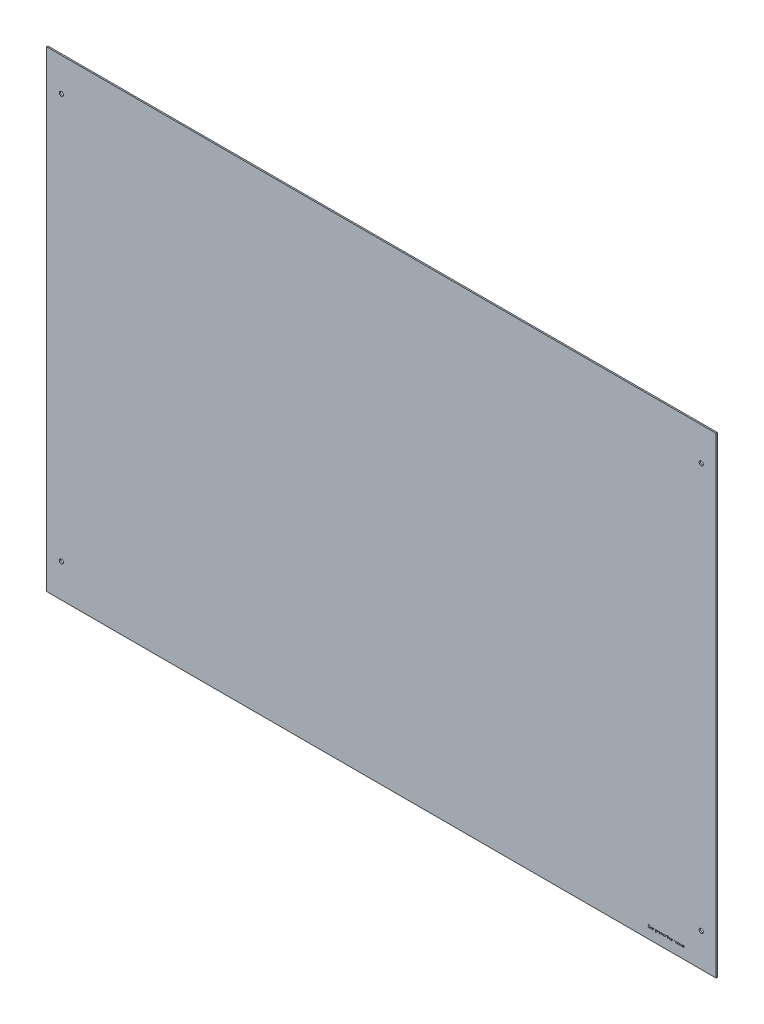
SolidWorks part; units mm, degrees
ref_plane "Front Plane" through (0, 0, 0) normal (0, 0, 1) x (1, 0, 0)
ref_plane "Top Plane" through (0, 0, 0) normal (0, 1, 0) x (1, 0, 0)
ref_plane "Right Plane" through (0, 0, 0) normal (1, 0, 0) x (0, 0, -1)
sketch "Sketch1" plane through (0, 0, 0) normal (0, 0, 1) x (1, 0, 0)
  line L0 (22, 655) -> (926.344, 655) construction
  line L1 (0, 0) -> (1000, 0)
  line L2 (0, 0) -> (0, 705)
  line L3 (0, 705) -> (1000, 705)
  line L4 (1000, 0) -> (1000, 705)
  line L5 (22, 655) -> (22, -22.1798) construction
  line L6 (22, 50) -> (969.7641, 50) construction
  line L7 (978, 655) -> (978, 40.8746) construction
  circle A0 centre (22, 655) radius 3.1
  circle A1 centre (22, 50) radius 3.1
  circle A2 centre (978, 50) radius 3.1
  circle A3 centre (978, 655) radius 3.1
  dimension "D7" = 6.2
  dimension "D1" = 1000
  dimension "D2" = 705
  dimension "D3" = 22
  dimension "D4" = 22
  dimension "D5" = 50
  dimension "D6" = 50
extrude "Boss-Extrude1" add sketch "Sketch1" along normal blind 2
sketch "Sketch2" plane through (0, 0, 2) normal (0, 0, 1) x (1, 0, 0)
  line L0 (897.8686, 15.1529) -> (992.3579, 15.1529) construction
  line L1 (901.5481, 18.0106) -> (901.2733, 17.8003)
  line L2 (901.2733, 16.0054) -> (901.5481, 15.7972)
  line L3 (905.3622, 17.7106) -> (905.6763, 17.7106)
  line L4 (905.6763, 17.7106) -> (905.6763, 17.266)
  line L5 (909.1763, 16.5383) -> (909.1763, 15.1529)
  line L6 (909.1763, 15.1529) -> (908.8622, 15.1529)
  line L7 (908.8622, 15.1529) -> (908.8622, 16.5397)
  line L8 (907.4263, 16.1478) -> (907.4263, 15.1529)
  line L9 (907.4263, 15.1529) -> (907.1122, 15.1529)
  line L10 (907.1122, 15.1529) -> (907.1122, 16.4534)
  line L11 (905.6763, 16.2291) -> (905.6763, 15.1529)
  line L12 (905.6763, 15.1529) -> (905.3622, 15.1529)
  line L13 (905.3622, 15.1529) -> (905.3622, 17.7106)
  line L14 (909.8942, 17.7106) -> (910.2083, 17.7106)
  line L15 (910.2083, 17.7106) -> (910.2083, 17.2373)
  line L16 (910.2083, 15.6163) -> (910.2083, 14.2106)
  line L17 (910.2083, 14.2106) -> (909.8942, 14.2106)
  line L18 (909.8942, 14.2106) -> (909.8942, 17.7106)
  line L19 (913.125, 17.7106) -> (913.4391, 17.7106)
  line L20 (913.4391, 17.7106) -> (913.4391, 17.3341)
  line L21 (914.3366, 17.6678) -> (914.1641, 17.3958)
  line L22 (913.4391, 16.0124) -> (913.4391, 15.1529)
  line L23 (913.4391, 15.1529) -> (913.125, 15.1529)
  line L24 (913.125, 15.1529) -> (913.125, 17.7106)
  line L25 (916.7498, 15.9606) -> (917.0289, 15.814)
  line L26 (917.1635, 16.3644) -> (914.875, 16.3644)
  line L27 (914.908, 16.6785) -> (916.8494, 16.6785)
  line L28 (919.0032, 17.3915) -> (918.7901, 17.1721)
  line L29 (917.5673, 15.4543) -> (917.7756, 15.6913)
  line L30 (920.8878, 17.3915) -> (920.6747, 17.1721)
  line L31 (919.4519, 15.4543) -> (919.6602, 15.6913)
  line L32 (924.6571, 17.7106) -> (924.9712, 17.7106)
  line L33 (924.9712, 17.7106) -> (924.9712, 17.3341)
  line L34 (925.8686, 17.6678) -> (925.6961, 17.3958)
  line L35 (924.9712, 16.0124) -> (924.9712, 15.1529)
  line L36 (924.9712, 15.1529) -> (924.6571, 15.1529)
  line L37 (924.6571, 15.1529) -> (924.6571, 17.7106)
  line L38 (928.6058, 18.7216) -> (928.6058, 18.3949)
  line L39 (928.0246, 18.0653) -> (928.0246, 17.7106)
  line L40 (928.0246, 17.7106) -> (928.5609, 17.7106)
  line L41 (928.5609, 17.7106) -> (928.5609, 17.3965)
  line L42 (928.5609, 17.3965) -> (928.0239, 17.3965)
  line L43 (928.0239, 17.3965) -> (928.0224, 15.1529)
  line L44 (928.0224, 15.1529) -> (927.7083, 15.1529)
  line L45 (927.7083, 15.1529) -> (927.7083, 17.3965)
  line L46 (927.7083, 17.3965) -> (927.3494, 17.3965)
  line L47 (927.3494, 17.3965) -> (927.3494, 17.7106)
  line L48 (927.3494, 17.7106) -> (927.7083, 17.7106)
  line L49 (927.7083, 17.7106) -> (927.7083, 18.1193)
  line L50 (928.9648, 17.7106) -> (929.2789, 17.7106)
  line L51 (929.2789, 17.7106) -> (929.2789, 17.3341)
  line L52 (930.1763, 17.6678) -> (930.0038, 17.3958)
  line L53 (929.2789, 16.0124) -> (929.2789, 15.1529)
  line L54 (929.2789, 15.1529) -> (928.9648, 15.1529)
  line L55 (928.9648, 15.1529) -> (928.9648, 17.7106)
  line L56 (933.6763, 17.7106) -> (933.9904, 17.7106)
  line L57 (933.9904, 17.7106) -> (933.9904, 17.2492)
  line L58 (935.9199, 16.4591) -> (935.9199, 15.1529)
  line L59 (935.9199, 15.1529) -> (935.6058, 15.1529)
  line L60 (935.6058, 15.1529) -> (935.6058, 16.356)
  line L61 (933.9904, 16.0776) -> (933.9904, 15.1529)
  line L62 (933.9904, 15.1529) -> (933.6763, 15.1529)
  line L63 (933.6763, 15.1529) -> (933.6763, 17.7106)
  line L64 (936.9519, 18.7426) -> (937.266, 18.7426)
  line L65 (937.266, 18.7426) -> (937.266, 17.7106)
  line L66 (937.266, 17.7106) -> (937.7148, 17.7106)
  line L67 (937.7148, 17.7106) -> (937.7148, 17.3965)
  line L68 (937.7148, 17.3965) -> (937.266, 17.3965)
  line L69 (937.266, 17.3965) -> (937.266, 15.1529)
  line L70 (937.266, 15.1529) -> (936.9519, 15.1529)
  line L71 (936.9519, 15.1529) -> (936.9519, 17.3965)
  line L72 (936.9519, 17.3965) -> (936.5032, 17.3965)
  line L73 (936.5032, 17.3965) -> (936.5032, 17.7106)
  line L74 (936.5032, 17.7106) -> (936.9519, 17.7106)
  line L75 (936.9519, 17.7106) -> (936.9519, 18.7426)
  line L76 (942.1122, 17.156) -> (941.8493, 16.9926)
  line L77 (941.8493, 15.8708) -> (942.1122, 15.6983)
  line L78 (945.6571, 17.7106) -> (945.9971, 17.7106)
  line L79 (945.9971, 17.7106) -> (946.8462, 15.8484)
  line L80 (946.8462, 15.8484) -> (947.6952, 17.7106)
  line L81 (947.6952, 17.7106) -> (948.0353, 17.7106)
  line L82 (948.0353, 17.7106) -> (946.8686, 15.1529)
  line L83 (946.8686, 15.1529) -> (946.8237, 15.1529)
  line L84 (946.8237, 15.1529) -> (945.6571, 17.7106)
  line L85 (950.6729, 15.9606) -> (950.9519, 15.814)
  line L86 (951.0866, 16.3644) -> (948.7981, 16.3644)
  line L87 (948.831, 16.6785) -> (950.7724, 16.6785)
  line L88 (951.625, 17.7106) -> (951.9391, 17.7106)
  line L89 (951.9391, 17.7106) -> (951.9391, 17.3341)
  line L90 (952.8366, 17.6678) -> (952.6641, 17.3958)
  line L91 (951.9391, 16.0124) -> (951.9391, 15.1529)
  line L92 (951.9391, 15.1529) -> (951.625, 15.1529)
  line L93 (951.625, 15.1529) -> (951.625, 17.7106)
  spline S0 degree 3 poles (901.2733, 17.8003) (901.235, 17.8473) (901.1744, 17.9145) (901.0867, 17.9963) (901.0188, 18.0536) (900.9471, 18.105) (900.8732, 18.1533) (900.796, 18.1965) (900.6892, 18.249) (900.5496, 18.3037) (900.3121, 18.3661) (900.1266, 18.3842) (900.0014, 18.3836) knots 0 0 0 0 0.125475 0.187121 0.248294 0.309295 0.36985 0.430973 0.492456 0.616148 0.740844 1 1 1 1
  spline S1 degree 3 poles (900.0014, 18.3836) (899.9315, 18.3846) (899.8276, 18.3771) (899.6911, 18.3569) (899.5914, 18.3348) (899.4938, 18.3068) (899.3977, 18.2734) (899.3045, 18.232) (899.2129, 18.1863) (899.1251, 18.1347) (899.0421, 18.0784) (898.9641, 18.018) (898.891, 17.9534) (898.8228, 17.8847) (898.76, 17.8114) (898.7028, 17.7335) (898.6501, 17.6522) (898.6029, 17.5677) (898.5634, 17.4796) (898.5284, 17.3895) (898.5007, 17.2963) (898.4788, 17.2008) (898.4583, 17.0686) (898.4511, 16.9676) (898.4519, 16.8994) knots 0 0 0 0 0.087502 0.130463 0.172752 0.215403 0.25765 0.300153 0.343121 0.385925 0.427686 0.468818 0.509492 0.549883 0.58998 0.630405 0.670869 0.711384 0.751627 0.791776 0.832459 0.873319 0.914543 1 1 1 1
  spline S2 degree 3 poles (898.4519, 16.8994) (898.4515, 16.7978) (898.4656, 16.6477) (898.5113, 16.4548) (898.5614, 16.3194) (898.6234, 16.1895) (898.7016, 16.0672) (898.7922, 15.9508) (898.8965, 15.843) (899.0109, 15.7445) (899.1336, 15.6577) (899.2644, 15.5854) (899.4018, 15.5252) (899.5468, 15.479) (899.7535, 15.4346) (899.9142, 15.4212) (900.0232, 15.4221) knots 0 0 0 0 0.12629 0.186726 0.246146 0.305576 0.365429 0.426326 0.48884 0.551725 0.613919 0.675484 0.737334 0.800229 0.864502 1 1 1 1
  spline S3 degree 3 poles (900.0232, 15.4221) (900.1433, 15.4221) (900.3218, 15.439) (900.5497, 15.501) (900.711, 15.5648) (900.8643, 15.6479) (901.0619, 15.7842) (901.1925, 15.9126) (901.2733, 16.0054) knots 0 0 0 0 0.252949 0.374755 0.49594 0.617181 0.740909 1 1 1 1
  spline S4 degree 3 poles (901.5481, 15.7972) (901.5048, 15.7397) (901.436, 15.657) (901.3351, 15.556) (901.2555, 15.4858) (901.1723, 15.4197) (901.0843, 15.3594) (900.9924, 15.3041) (900.897, 15.2534) (900.7983, 15.2085) (900.6963, 15.1701) (900.5915, 15.1369) (900.4838, 15.1097) (900.3731, 15.0884) (900.2203, 15.0691) (900.1037, 15.0626) (900.0253, 15.0631) knots 0 0 0 0 0.123053 0.183475 0.243727 0.304279 0.364863 0.425946 0.487391 0.54922 0.611144 0.673529 0.736961 0.800785 0.866013 1 1 1 1
  spline S5 degree 3 poles (900.0253, 15.0631) (899.9508, 15.0622) (899.8407, 15.0682) (899.6963, 15.0838) (899.5925, 15.101) (899.4914, 15.1213) (899.3938, 15.1486) (899.2989, 15.1792) (899.2069, 15.2151) (899.1178, 15.2556) (899.032, 15.3014) (898.9494, 15.352) (898.8691, 15.4065) (898.7926, 15.4665) (898.6937, 15.5531) (898.6247, 15.6246) (898.5816, 15.6752) knots 0 0 0 0 0.13775 0.203917 0.26878 0.332414 0.394754 0.45618 0.516996 0.577396 0.637198 0.696999 0.756756 0.816554 0.876948 1 1 1 1
  spline S6 degree 3 poles (898.5816, 15.6752) (898.5091, 15.7599) (898.4116, 15.8957) (898.3085, 16.0921) (898.2461, 16.2455) (898.1974, 16.4055) (898.1514, 16.631) (898.1375, 16.8054) (898.1378, 16.9232) knots 0 0 0 0 0.247156 0.36878 0.490734 0.613614 0.738958 1 1 1 1
  spline S7 degree 3 poles (898.1378, 16.9232) (898.1378, 17.047) (898.1535, 17.2305) (898.2103, 17.4659) (898.2696, 17.6321) (898.345, 17.7913) (898.438, 17.9421) (898.5477, 18.0856) (898.6731, 18.2196) (898.8107, 18.3422) (898.958, 18.45) (899.1148, 18.5397) (899.2793, 18.6147) (899.4528, 18.6723) (899.6994, 18.7272) (899.8912, 18.7424) (900.021, 18.7426) knots 0 0 0 0 0.127014 0.187955 0.248014 0.307748 0.368235 0.42947 0.492743 0.556258 0.618217 0.679655 0.741246 0.803415 0.866815 1 1 1 1
  spline S8 degree 3 poles (900.021, 18.7426) (900.1006, 18.7428) (900.2187, 18.7374) (900.3733, 18.7163) (900.4849, 18.6952) (900.594, 18.669) (900.6998, 18.6349) (900.8029, 18.5959) (900.9026, 18.5509) (900.9986, 18.5004) (901.0906, 18.445) (901.1781, 18.3847) (901.2616, 18.3201) (901.3397, 18.2497) (901.4399, 18.1505) (901.5059, 18.0674) (901.5481, 18.0106) knots 0 0 0 0 0.135683 0.201215 0.265682 0.329267 0.392395 0.45507 0.517127 0.57879 0.63974 0.700192 0.759806 0.819628 0.879355 1 1 1 1
  spline S9 degree 3 poles (903.4117, 17.7554) (903.5058, 17.7564) (903.645, 17.7428) (903.8231, 17.6982) (903.9489, 17.653) (904.0673, 17.5923) (904.2197, 17.4947) (904.3213, 17.402) (904.3834, 17.3341) knots 0 0 0 0 0.258332 0.382134 0.503804 0.624693 0.746871 1 1 1 1
  spline S10 degree 3 poles (904.3834, 17.3341) (904.4405, 17.2717) (904.5169, 17.1718) (904.5991, 17.0274) (904.6482, 16.9152) (904.6868, 16.7988) (904.724, 16.6359) (904.7335, 16.5096) (904.734, 16.4247) knots 0 0 0 0 0.253834 0.376506 0.498534 0.621368 0.744565 1 1 1 1
  spline S11 degree 3 poles (904.734, 16.4247) (904.7345, 16.3391) (904.7228, 16.212) (904.6842, 16.0476) (904.6434, 15.9298) (904.591, 15.8159) (904.5271, 15.7065) (904.4512, 15.6013) (904.3652, 15.5013) (904.2702, 15.4092) (904.1671, 15.3288) (904.0579, 15.26) (903.9413, 15.2046) (903.8182, 15.1609) (903.6421, 15.119) (903.5046, 15.1084) (903.4117, 15.108) knots 0 0 0 0 0.123337 0.183265 0.243172 0.302898 0.363774 0.425605 0.489659 0.553785 0.616222 0.677854 0.739517 0.802097 0.865866 1 1 1 1
  spline S12 degree 3 poles (903.4117, 15.108) (903.3183, 15.1084) (903.1802, 15.1189) (903.0037, 15.1609) (902.8805, 15.2047) (902.7634, 15.26) (902.6536, 15.3286) (902.5504, 15.4092) (902.4553, 15.5013) (902.3693, 15.6013) (902.2934, 15.7065) (902.2295, 15.8159) (902.1772, 15.9298) (902.1364, 16.0476) (902.0978, 16.212) (902.086, 16.3391) (902.0866, 16.4247) knots 0 0 0 0 0.134635 0.198324 0.260825 0.322714 0.384555 0.446913 0.510958 0.574931 0.636685 0.697483 0.757134 0.816966 0.876818 1 1 1 1
  spline S13 degree 3 poles (902.0866, 16.4247) (902.087, 16.5094) (902.0966, 16.6354) (902.1336, 16.7979) (902.1723, 16.9138) (902.2218, 17.0256) (902.303, 17.1703) (902.3807, 17.2694) (902.4371, 17.332) knots 0 0 0 0 0.255238 0.378679 0.501088 0.622714 0.746241 1 1 1 1
  spline S14 degree 3 poles (902.4371, 17.332) (902.4987, 17.4008) (902.6013, 17.4926) (902.7533, 17.5922) (902.8729, 17.6517) (902.9986, 17.6985) (903.1775, 17.7428) (903.3171, 17.7563) (903.4117, 17.7554) knots 0 0 0 0 0.252713 0.374819 0.496436 0.617911 0.741288 1 1 1 1
  spline S15 degree 3 poles (903.4103, 17.4413) (903.3433, 17.4412) (903.2437, 17.4321) (903.1158, 17.401) (903.0243, 17.3684) (902.9367, 17.3263) (902.8528, 17.2746) (902.7724, 17.214) (902.697, 17.1445) (902.6278, 17.0686) (902.5673, 16.9878) (902.5159, 16.9033) (902.473, 16.815) (902.4412, 16.7221) (902.4097, 16.592) (902.4008, 16.4907) (902.4007, 16.4226) knots 0 0 0 0 0.126044 0.187165 0.247399 0.30838 0.36978 0.432584 0.497641 0.562401 0.625557 0.687332 0.748313 0.809791 0.871768 1 1 1 1
  spline S16 degree 3 poles (902.4007, 16.4226) (902.4009, 16.3339) (902.4165, 16.2006) (902.4748, 16.0326) (902.5333, 15.913) (902.6068, 15.8023) (902.6933, 15.7037) (902.7919, 15.6185) (902.9015, 15.5478) (903.0199, 15.4917) (903.1883, 15.4378) (903.321, 15.4211) (903.4103, 15.4221) knots 0 0 0 0 0.168179 0.251488 0.335841 0.419834 0.502345 0.583649 0.665931 0.748717 0.831047 1 1 1 1
  spline S17 degree 3 poles (903.4103, 15.4221) (903.4995, 15.4212) (903.6321, 15.4376) (903.8001, 15.4919) (903.9184, 15.5477) (904.0279, 15.6188) (904.1273, 15.7032) (904.213, 15.8026) (904.2864, 15.9132) (904.3459, 16.0324) (904.4039, 16.2007) (904.4197, 16.3339) (904.4199, 16.4226) knots 0 0 0 0 0.168983 0.250908 0.333708 0.416005 0.49766 0.579893 0.663902 0.748466 0.831791 1 1 1 1
  spline S18 degree 3 poles (904.4199, 16.4226) (904.4197, 16.4907) (904.4108, 16.5919) (904.3794, 16.7222) (904.3474, 16.815) (904.3048, 16.9035) (904.2524, 16.9875) (904.1921, 17.0689) (904.1221, 17.1443) (904.0468, 17.214) (903.9664, 17.2746) (903.8826, 17.3261) (903.7952, 17.3688) (903.7037, 17.4007) (903.5762, 17.4323) (903.477, 17.441) (903.4103, 17.4413) knots 0 0 0 0 0.128274 0.19027 0.251768 0.312769 0.374793 0.43797 0.503047 0.568125 0.63095 0.692369 0.752973 0.813641 0.874355 1 1 1 1
  spline S19 degree 3 poles (905.6763, 17.266) (905.729, 17.3415) (905.8354, 17.4744) (905.9654, 17.5845) (906.0311, 17.6257) knots 0 0 0 0 0.543395 1 1 1 1
  spline S20 degree 3 poles (906.0311, 17.6257) (906.1127, 17.6679) (906.2845, 17.7345) (906.4676, 17.7547) (906.5583, 17.7554) knots 0 0 0 0 0.503035 1 1 1 1
  spline S21 degree 3 poles (906.5583, 17.7554) (906.6194, 17.7546) (906.711, 17.7469) (906.8288, 17.7156) (906.9134, 17.6832) (906.9931, 17.6439) (907.0662, 17.5979) (907.1318, 17.5462) (907.19, 17.4865) (907.2422, 17.4172) (907.31, 17.3034) (907.3488, 17.2064) (907.3723, 17.1377) knots 0 0 0 0 0.166532 0.248836 0.331246 0.412957 0.490494 0.566156 0.639987 0.716765 0.802144 1 1 1 1
  spline S22 degree 3 poles (907.3723, 17.1377) (907.3984, 17.1869) (907.4415, 17.2573) (907.5058, 17.3444) (907.5558, 17.4044) (907.6082, 17.4597) (907.6633, 17.5105) (907.7207, 17.557) (907.8005, 17.6113) (907.9043, 17.669) (908.0789, 17.7361) (908.218, 17.7557) (908.3104, 17.7554) knots 0 0 0 0 0.141226 0.209116 0.27484 0.339483 0.402476 0.464942 0.526833 0.647415 0.765562 1 1 1 1
  spline S23 degree 3 poles (908.3104, 17.7554) (908.3941, 17.7548) (908.5191, 17.7411) (908.6733, 17.6831) (908.7788, 17.6249) (908.874, 17.5517) (908.9567, 17.4646) (909.0265, 17.3643) (909.072, 17.2699) (909.103, 17.1866) (909.122, 17.1156) (909.1389, 17.0374) (909.1528, 16.952) (909.163, 16.8591) (909.1736, 16.7205) (909.1767, 16.6126) (909.1763, 16.5383) knots 0 0 0 0 0.147965 0.218797 0.28947 0.359724 0.429708 0.500497 0.574429 0.613947 0.657155 0.703973 0.754939 0.809707 0.868833 1 1 1 1
  spline S24 degree 3 poles (908.8622, 16.5397) (908.8623, 16.6026) (908.8613, 16.6929) (908.8542, 16.8078) (908.8483, 16.882) (908.84, 16.9482) (908.8294, 17.0064) (908.8181, 17.057) (908.7994, 17.1131) (908.7694, 17.175) (908.7238, 17.2417) (908.6663, 17.2998) (908.6, 17.3502) (908.5244, 17.3912) (908.4106, 17.4314) (908.3182, 17.4417) (908.2557, 17.4413) knots 0 0 0 0 0.150563 0.216151 0.27568 0.328707 0.375904 0.417302 0.452693 0.517265 0.581217 0.645322 0.712024 0.78013 0.850218 1 1 1 1
  spline S25 degree 3 poles (908.2557, 17.4413) (908.1772, 17.4427) (908.0602, 17.4234) (907.9132, 17.3654) (907.811, 17.303) (907.717, 17.2282) (907.6361, 17.1393) (907.5693, 17.0386) (907.524, 16.9455) (907.4954, 16.8618) (907.4765, 16.7887) (907.4619, 16.7056) (907.4481, 16.6131) (907.4391, 16.5106) (907.4277, 16.3546) (907.4268, 16.2323) (907.4263, 16.1478) knots 0 0 0 0 0.134707 0.201865 0.270788 0.340024 0.408083 0.476813 0.547346 0.58564 0.628865 0.677153 0.730803 0.789807 0.854325 1 1 1 1
  spline S26 degree 3 poles (907.1122, 16.4534) (907.1122, 16.524) (907.1113, 16.6253) (907.1042, 16.7541) (907.0983, 16.8369) (907.0899, 16.9103) (907.0802, 16.9747) (907.0689, 17.0299) (907.0501, 17.0905) (907.0214, 17.1572) (906.9752, 17.2283) (906.9176, 17.2906) (906.85, 17.3438) (906.774, 17.3877) (906.6596, 17.431) (906.5663, 17.4408) (906.5036, 17.4413) knots 0 0 0 0 0.158779 0.227738 0.289946 0.345499 0.393896 0.436374 0.472122 0.536384 0.599078 0.661948 0.726311 0.791771 0.858647 1 1 1 1
  spline S27 degree 3 poles (906.5036, 17.4413) (906.4278, 17.442) (906.3139, 17.4238) (906.1711, 17.3662) (906.0691, 17.3066) (905.9754, 17.2327) (905.8934, 17.1458) (905.8245, 17.047) (905.7787, 16.9548) (905.7492, 16.8732) (905.7296, 16.8039) (905.7128, 16.7269) (905.7003, 16.642) (905.6882, 16.5498) (905.68, 16.4112) (905.6753, 16.3035) (905.6763, 16.2291) knots 0 0 0 0 0.136871 0.206114 0.277538 0.349772 0.421251 0.492911 0.567027 0.606614 0.649704 0.697303 0.749086 0.804881 0.865485 1 1 1 1
  spline S28 degree 3 poles (910.2083, 17.2373) (910.2705, 17.3226) (910.3749, 17.4385) (910.5362, 17.5627) (910.6633, 17.6341) (910.7978, 17.6879) (910.989, 17.7421) (911.1401, 17.7551) (911.2418, 17.7554) knots 0 0 0 0 0.263045 0.386061 0.505771 0.625178 0.746148 1 1 1 1
  spline S29 degree 3 poles (911.2418, 17.7554) (911.3314, 17.7545) (911.4647, 17.7446) (911.6362, 17.7038) (911.7577, 17.6604) (911.875, 17.6068) (911.9862, 17.5391) (912.0931, 17.4607) (912.193, 17.3704) (912.2854, 17.2728) (912.3652, 17.1678) (912.4341, 17.0588) (912.4897, 16.9442) (912.5333, 16.8249) (912.5753, 16.6572) (912.586, 16.5265) (912.5866, 16.4387) knots 0 0 0 0 0.128636 0.190653 0.252125 0.313446 0.375227 0.438498 0.503285 0.56801 0.630879 0.692154 0.752552 0.813191 0.873985 1 1 1 1
  spline S30 degree 3 poles (912.5866, 16.4387) (912.5863, 16.3492) (912.5748, 16.2165) (912.5342, 16.0458) (912.4912, 15.9245) (912.4355, 15.8085) (912.3678, 15.6979) (912.2879, 15.5927) (912.1966, 15.4944) (912.0976, 15.4038) (911.9917, 15.3246) (911.8806, 15.258) (911.765, 15.2024) (911.6437, 15.1606) (911.4734, 15.1196) (911.3409, 15.1083) (911.2516, 15.108) knots 0 0 0 0 0.128034 0.189574 0.25058 0.311733 0.37325 0.435763 0.500346 0.564949 0.627528 0.689157 0.749865 0.81076 0.8723 1 1 1 1
  spline S31 degree 3 poles (911.2516, 15.108) (911.1511, 15.1068) (911.0026, 15.124) (910.8123, 15.1766) (910.6781, 15.2332) (910.55, 15.3055) (910.3849, 15.425) (910.2759, 15.5362) (910.2083, 15.6163) knots 0 0 0 0 0.250548 0.37123 0.492116 0.613401 0.737997 1 1 1 1
  spline S32 degree 3 poles (911.239, 17.4413) (911.1689, 17.4424) (911.0655, 17.4323) (910.9318, 17.4027) (910.8377, 17.3698) (910.7474, 17.3294) (910.6617, 17.2789) (910.5807, 17.2193) (910.5045, 17.1516) (910.4356, 17.077) (910.3746, 16.9974) (910.3234, 16.9129) (910.2809, 16.8243) (910.2486, 16.7309) (910.2174, 16.5987) (910.2085, 16.4956) (910.2083, 16.4261) knots 0 0 0 0 0.130024 0.192374 0.253884 0.314896 0.375806 0.438242 0.501591 0.564881 0.626533 0.687516 0.748106 0.808796 0.870822 1 1 1 1
  spline S33 degree 3 poles (910.2083, 16.4261) (910.2085, 16.3353) (910.2236, 16.2002) (910.2797, 16.0304) (910.3381, 15.9129) (910.4121, 15.805) (910.5012, 15.7083) (910.6046, 15.6235) (910.7207, 15.552) (910.8451, 15.4941) (911.0183, 15.4384) (911.1538, 15.4223) (911.2439, 15.4221) knots 0 0 0 0 0.169344 0.251061 0.332326 0.413189 0.494299 0.576654 0.661785 0.747765 0.831967 1 1 1 1
  spline S34 degree 3 poles (911.2439, 15.4221) (911.3324, 15.4216) (911.4646, 15.4395) (911.6335, 15.4944) (911.7537, 15.5539) (911.8665, 15.6269) (911.9684, 15.7144) (912.0574, 15.8159) (912.1333, 15.9289) (912.1943, 16.0501) (912.2556, 16.2165) (912.2714, 16.3484) (912.2724, 16.4352) knots 0 0 0 0 0.165574 0.248159 0.332033 0.416257 0.499525 0.583039 0.668596 0.754035 0.83692 1 1 1 1
  spline S35 degree 3 poles (912.2724, 16.4352) (912.2737, 16.5227) (912.2541, 16.6537) (912.1966, 16.8211) (912.1341, 16.9406) (912.0599, 17.0534) (911.9701, 17.1529) (911.8695, 17.2401) (911.7568, 17.3121) (911.6359, 17.3694) (911.4649, 17.4259) (911.3295, 17.4409) (911.239, 17.4413) knots 0 0 0 0 0.163349 0.245826 0.330367 0.415198 0.497941 0.580476 0.66374 0.747513 0.830399 1 1 1 1
  spline S36 degree 3 poles (913.4391, 17.3341) (913.4821, 17.4018) (913.5501, 17.4955) (913.6559, 17.5982) (913.7335, 17.6568) (913.8139, 17.7005) (913.9215, 17.7432) (914.007, 17.755) (914.0631, 17.7554) knots 0 0 0 0 0.306112 0.438367 0.560541 0.675317 0.786114 1 1 1 1
  spline S37 degree 3 poles (914.0631, 17.7554) (914.1081, 17.7551) (914.2046, 17.7382) (914.2922, 17.6947) (914.3366, 17.6678) knots 0 0 0 0 0.463523 1 1 1 1
  spline S38 degree 3 poles (914.1641, 17.3958) (914.1355, 17.4084) (914.084, 17.4317) (914.0282, 17.441) (914.0035, 17.4413) knots 0 0 0 0 0.56023 1 1 1 1
  spline S39 degree 3 poles (914.0035, 17.4413) (913.952, 17.4414) (913.8731, 17.4225) (913.7782, 17.3657) (913.72, 17.3175) (913.675, 17.2709) (913.6428, 17.2303) (913.6133, 17.1847) (913.5852, 17.135) (913.5595, 17.0803) (913.5266, 16.9992) (913.5071, 16.9347) (913.4952, 16.8902) knots 0 0 0 0 0.191338 0.295191 0.410312 0.47193 0.536425 0.603119 0.674118 0.749332 0.828283 1 1 1 1
  spline S40 degree 3 poles (913.4952, 16.8902) (913.4835, 16.8456) (913.472, 16.7704) (913.4598, 16.6607) (913.4526, 16.5577) (913.4461, 16.4411) (913.4408, 16.2579) (913.4386, 16.1134) (913.4391, 16.0124) knots 0 0 0 0 0.156938 0.2586 0.375891 0.508166 0.656238 1 1 1 1
  spline S41 degree 3 poles (917.0289, 15.814) (916.9874, 15.7363) (916.9179, 15.6273) (916.8109, 15.4976) (916.7259, 15.4158) (916.6362, 15.3446) (916.5415, 15.2822) (916.4412, 15.2291) (916.3353, 15.1844) (916.223, 15.15) (916.0606, 15.1167) (915.9338, 15.108) (915.8475, 15.108) knots 0 0 0 0 0.181661 0.265874 0.346355 0.4246 0.501903 0.579992 0.658443 0.738672 0.821894 1 1 1 1
  spline S42 degree 3 poles (915.8475, 15.108) (915.7517, 15.108) (915.6108, 15.119) (915.4315, 15.1622) (915.3083, 15.2061) (915.1936, 15.2635) (915.0871, 15.3335) (914.9883, 15.4156) (914.9002, 15.5106) (914.821, 15.6123) (914.7511, 15.7183) (914.6926, 15.8282) (914.6451, 15.9415) (914.6067, 16.0574) (914.5706, 16.2178) (914.5618, 16.3417) (914.5609, 16.4247) knots 0 0 0 0 0.139629 0.204797 0.268135 0.329814 0.391301 0.453434 0.516552 0.579631 0.641119 0.701294 0.76081 0.819932 0.87892 1 1 1 1
  spline S43 degree 3 poles (914.5609, 16.4247) (914.5619, 16.5025) (914.5691, 16.6186) (914.6008, 16.7692) (914.6329, 16.8781) (914.6745, 16.9836) (914.7427, 17.1211) (914.8078, 17.2172) (914.8554, 17.2787) knots 0 0 0 0 0.253768 0.377428 0.500551 0.623296 0.746578 1 1 1 1
  spline S44 degree 3 poles (914.8554, 17.2787) (914.916, 17.3544) (915.0147, 17.4603) (915.1694, 17.571) (915.291, 17.6391) (915.4213, 17.6907) (915.6078, 17.7432) (915.7557, 17.7542) (915.8552, 17.7554) knots 0 0 0 0 0.253589 0.374643 0.49534 0.616325 0.739759 1 1 1 1
  spline S45 degree 3 poles (915.8552, 17.7554) (915.958, 17.7559) (916.1099, 17.741) (916.3025, 17.6877) (916.4364, 17.6326) (916.562, 17.5614) (916.7203, 17.4423) (916.8237, 17.3327) (916.8851, 17.252) knots 0 0 0 0 0.259033 0.38188 0.502258 0.622752 0.744743 1 1 1 1
  spline S46 degree 3 poles (916.8851, 17.252) (916.931, 17.1931) (916.9909, 17.0975) (917.0545, 16.9607) (917.0929, 16.8518) (917.1239, 16.738) (917.1545, 16.5756) (917.1619, 16.4497) (917.1635, 16.3644) knots 0 0 0 0 0.236255 0.356174 0.47725 0.60154 0.729618 1 1 1 1
  spline S47 degree 3 poles (914.875, 16.3644) (914.8768, 16.2982) (914.8857, 16.2003) (914.916, 16.0751) (914.9472, 15.988) (914.9851, 15.9051) (915.0315, 15.8269) (915.0868, 15.7539) (915.1485, 15.6853) (915.2172, 15.6242) (915.2895, 15.5696) (915.3664, 15.5238) (915.4473, 15.4866) (915.5321, 15.4575) (915.6521, 15.4305) (915.7452, 15.4217) (915.8082, 15.4221) knots 0 0 0 0 0.134476 0.198391 0.260753 0.321829 0.383037 0.444653 0.507398 0.569825 0.630778 0.690929 0.750945 0.811049 0.872331 1 1 1 1
  spline S48 degree 3 poles (915.8082, 15.4221) (915.8704, 15.4218) (915.9637, 15.4291) (916.0855, 15.4546) (916.1748, 15.4805) (916.2604, 15.5121) (916.3396, 15.5502) (916.4125, 15.5923) (916.4806, 15.6405) (916.5467, 15.6996) (916.6402, 15.8044) (916.7073, 15.894) (916.7498, 15.9606) knots 0 0 0 0 0.163879 0.245659 0.327726 0.40861 0.485749 0.559169 0.630268 0.705306 0.792065 1 1 1 1
  spline S49 degree 3 poles (916.8494, 16.6785) (916.8295, 16.7592) (916.7899, 16.8732) (916.7174, 17.0101) (916.6558, 17.0957) (916.586, 17.1717) (916.5054, 17.2381) (916.4149, 17.2975) (916.3152, 17.3477) (916.2095, 17.3903) (916.0617, 17.4289) (915.9477, 17.4425) (915.8713, 17.4413) knots 0 0 0 0 0.185231 0.267501 0.3444 0.419595 0.496891 0.576638 0.660268 0.745387 0.83004 1 1 1 1
  spline S50 degree 3 poles (915.8713, 17.4413) (915.8094, 17.4415) (915.7173, 17.4348) (915.599, 17.4091) (915.5143, 17.3831) (915.4337, 17.3485) (915.3287, 17.2941) (915.2578, 17.2398) (915.2123, 17.2015) knots 0 0 0 0 0.259141 0.384162 0.505992 0.629098 0.750669 1 1 1 1
  spline S51 degree 3 poles (915.2123, 17.2015) (915.1774, 17.1722) (915.1302, 17.1213) (915.0734, 17.0465) (915.0341, 16.9835) (914.998, 16.9149) (914.9518, 16.8142) (914.9244, 16.7338) (914.908, 16.6785) knots 0 0 0 0 0.22258 0.3385 0.458709 0.585535 0.717518 1 1 1 1
  spline S52 degree 3 poles (918.7901, 17.1721) (918.7553, 17.2136) (918.7018, 17.2716) (918.624, 17.3356) (918.5689, 17.3745) (918.5135, 17.4039) (918.4414, 17.4322) (918.3852, 17.4413) (918.3484, 17.4413) knots 0 0 0 0 0.305036 0.441309 0.565963 0.683525 0.793334 1 1 1 1
  spline S53 degree 3 poles (918.3484, 17.4413) (918.3047, 17.4422) (918.2396, 17.4281) (918.1623, 17.3846) (918.1121, 17.3387) (918.0697, 17.2859) (918.028, 17.207) (918.0162, 17.141) (918.016, 17.0971) knots 0 0 0 0 0.245901 0.369166 0.498511 0.628504 0.751028 1 1 1 1
  spline S54 degree 3 poles (918.016, 17.0971) (918.0161, 17.0567) (918.0318, 16.9726) (918.0763, 16.8995) (918.103, 16.865) knots 0 0 0 0 0.479403 1 1 1 1
  spline S55 degree 3 poles (918.103, 16.865) (918.119, 16.8433) (918.1502, 16.8138) (918.1957, 16.7736) (918.239, 16.7416) (918.2878, 16.708) (918.3646, 16.6606) (918.4248, 16.624) (918.4683, 16.6014) knots 0 0 0 0 0.17756 0.283982 0.402217 0.533568 0.676121 1 1 1 1
  spline S56 degree 3 poles (918.4683, 16.6014) (918.521, 16.5723) (918.5968, 16.5284) (918.6905, 16.4655) (918.752, 16.4209) (918.8059, 16.3757) (918.8676, 16.3195) (918.9067, 16.2737) (918.9289, 16.2424) knots 0 0 0 0 0.307115 0.446213 0.574876 0.694152 0.804581 1 1 1 1
  spline S57 degree 3 poles (918.9289, 16.2424) (918.967, 16.1849) (919.031, 16.0582) (919.0471, 15.9172) (919.0481, 15.847) knots 0 0 0 0 0.495235 1 1 1 1
  spline S58 degree 3 poles (919.0481, 15.847) (919.0476, 15.7973) (919.0421, 15.7232) (919.0191, 15.6284) (918.996, 15.5607) (918.9649, 15.4968) (918.9283, 15.435) (918.8844, 15.3766) (918.8343, 15.3217) (918.7795, 15.2717) (918.721, 15.2276) (918.6588, 15.1911) (918.5932, 15.1608) (918.5243, 15.1367) (918.4263, 15.1141) (918.35, 15.1083) (918.2986, 15.108) knots 0 0 0 0 0.127199 0.188597 0.24864 0.309525 0.370037 0.431889 0.495704 0.559519 0.621372 0.682397 0.743568 0.805498 0.86864 1 1 1 1
  spline S59 degree 3 poles (918.2986, 15.108) (918.2283, 15.1075) (918.1231, 15.1196) (917.9876, 15.1583) (917.8892, 15.198) (917.7962, 15.2482) (917.6829, 15.3277) (917.6096, 15.4008) (917.5673, 15.4543) knots 0 0 0 0 0.251724 0.377219 0.504694 0.631458 0.755401 1 1 1 1
  spline S60 degree 3 poles (917.7756, 15.6913) (917.8132, 15.6494) (917.8715, 15.5907) (917.9573, 15.5273) (918.0202, 15.4886) (918.0844, 15.4589) (918.1709, 15.4309) (918.238, 15.4219) (918.2825, 15.4221) knots 0 0 0 0 0.285904 0.417172 0.540501 0.659238 0.775006 1 1 1 1
  spline S61 degree 3 poles (918.2825, 15.4221) (918.3417, 15.4216) (918.4295, 15.4369) (918.5352, 15.4886) (918.6032, 15.5427) (918.6611, 15.6056) (918.7172, 15.7) (918.7343, 15.7804) (918.734, 15.8337) knots 0 0 0 0 0.261896 0.387836 0.517686 0.644509 0.764718 1 1 1 1
  spline S62 degree 3 poles (918.734, 15.8337) (918.7338, 15.8776) (918.7198, 15.9659) (918.6756, 16.0437) (918.6477, 16.0776) knots 0 0 0 0 0.500453 1 1 1 1
  spline S63 degree 3 poles (918.6477, 16.0776) (918.6309, 16.0979) (918.5997, 16.1273) (918.5518, 16.1654) (918.5067, 16.1978) (918.4547, 16.2314) (918.372, 16.28) (918.3064, 16.3168) (918.26, 16.3413) knots 0 0 0 0 0.167462 0.27227 0.389551 0.520801 0.666263 1 1 1 1
  spline S64 degree 3 poles (918.26, 16.3413) (918.2094, 16.3692) (918.1364, 16.4109) (918.0474, 16.4726) (917.9883, 16.5155) (917.9361, 16.5589) (917.8782, 16.6153) (917.84, 16.6594) (917.819, 16.6904) knots 0 0 0 0 0.30595 0.443775 0.572824 0.692154 0.802296 1 1 1 1
  spline S65 degree 3 poles (917.819, 16.6904) (917.7798, 16.7468) (917.7214, 16.8747) (917.7007, 17.0137) (917.7019, 17.0845) knots 0 0 0 0 0.492591 1 1 1 1
  spline S66 degree 3 poles (917.7019, 17.0845) (917.7023, 17.1306) (917.7064, 17.1992) (917.7271, 17.2868) (917.7461, 17.3489) (917.7726, 17.4074) (917.8042, 17.4631) (917.8414, 17.5158) (917.8843, 17.5648) (917.9314, 17.6093) (917.9823, 17.6481) (918.0358, 17.6812) (918.0922, 17.709) (918.152, 17.73) (918.2372, 17.7497) (918.3035, 17.756) (918.3484, 17.7554) knots 0 0 0 0 0.133044 0.196507 0.258613 0.319728 0.380873 0.442636 0.505079 0.567881 0.628814 0.68891 0.748765 0.809386 0.870884 1 1 1 1
  spline S67 degree 3 poles (918.3484, 17.7554) (918.4033, 17.7554) (918.4871, 17.7437) (918.595, 17.7052) (918.6774, 17.665) (918.7592, 17.6129) (918.8727, 17.5261) (918.9526, 17.4488) (919.0032, 17.3915) knots 0 0 0 0 0.213412 0.326127 0.444452 0.569061 0.702712 1 1 1 1
  spline S68 degree 3 poles (920.6747, 17.1721) (920.6399, 17.2136) (920.5864, 17.2716) (920.5086, 17.3356) (920.4535, 17.3745) (920.3981, 17.4039) (920.326, 17.4322) (920.2698, 17.4413) (920.233, 17.4413) knots 0 0 0 0 0.305036 0.441309 0.565963 0.683525 0.793334 1 1 1 1
  spline S69 degree 3 poles (920.233, 17.4413) (920.1893, 17.4422) (920.1242, 17.4281) (920.0469, 17.3846) (919.9967, 17.3387) (919.9543, 17.2859) (919.9126, 17.207) (919.9008, 17.141) (919.9007, 17.0971) knots 0 0 0 0 0.245901 0.369166 0.498511 0.628504 0.751028 1 1 1 1
  spline S70 degree 3 poles (919.9007, 17.0971) (919.9007, 17.0567) (919.9164, 16.9726) (919.9609, 16.8995) (919.9876, 16.865) knots 0 0 0 0 0.479403 1 1 1 1
  spline S71 degree 3 poles (919.9876, 16.865) (920.0036, 16.8433) (920.0348, 16.8138) (920.0804, 16.7736) (920.1236, 16.7416) (920.1724, 16.708) (920.2493, 16.6606) (920.3095, 16.624) (920.3529, 16.6014) knots 0 0 0 0 0.17756 0.283982 0.402217 0.533568 0.676121 1 1 1 1
  spline S72 degree 3 poles (920.3529, 16.6014) (920.4056, 16.5723) (920.4815, 16.5284) (920.5751, 16.4655) (920.6366, 16.4209) (920.6905, 16.3757) (920.7522, 16.3195) (920.7914, 16.2737) (920.8135, 16.2424) knots 0 0 0 0 0.307115 0.446213 0.574876 0.694152 0.804581 1 1 1 1
  spline S73 degree 3 poles (920.8135, 16.2424) (920.8516, 16.1849) (920.9156, 16.0582) (920.9317, 15.9172) (920.9327, 15.847) knots 0 0 0 0 0.495235 1 1 1 1
  spline S74 degree 3 poles (920.9327, 15.847) (920.9322, 15.7973) (920.9267, 15.7232) (920.9037, 15.6284) (920.8807, 15.5607) (920.8495, 15.4968) (920.8129, 15.435) (920.7691, 15.3766) (920.719, 15.3217) (920.6641, 15.2717) (920.6056, 15.2276) (920.5434, 15.1911) (920.4778, 15.1608) (920.4089, 15.1367) (920.3109, 15.1141) (920.2346, 15.1083) (920.1832, 15.108) knots 0 0 0 0 0.127199 0.188597 0.24864 0.309525 0.370037 0.431889 0.495704 0.559519 0.621372 0.682397 0.743568 0.805498 0.86864 1 1 1 1
  spline S75 degree 3 poles (920.1832, 15.108) (920.1129, 15.1075) (920.0077, 15.1196) (919.8722, 15.1583) (919.7738, 15.198) (919.6808, 15.2482) (919.5675, 15.3277) (919.4942, 15.4008) (919.4519, 15.4543) knots 0 0 0 0 0.251724 0.377219 0.504694 0.631458 0.755401 1 1 1 1
  spline S76 degree 3 poles (919.6602, 15.6913) (919.6978, 15.6494) (919.7561, 15.5907) (919.842, 15.5273) (919.9048, 15.4886) (919.969, 15.4589) (920.0555, 15.4309) (920.1226, 15.4219) (920.1671, 15.4221) knots 0 0 0 0 0.285904 0.417172 0.540501 0.659238 0.775006 1 1 1 1
  spline S77 degree 3 poles (920.1671, 15.4221) (920.2263, 15.4216) (920.3141, 15.4369) (920.4198, 15.4886) (920.4879, 15.5427) (920.5457, 15.6056) (920.6018, 15.7) (920.6189, 15.7804) (920.6186, 15.8337) knots 0 0 0 0 0.261896 0.387836 0.517686 0.644509 0.764718 1 1 1 1
  spline S78 degree 3 poles (920.6186, 15.8337) (920.6184, 15.8776) (920.6044, 15.9659) (920.5603, 16.0437) (920.5324, 16.0776) knots 0 0 0 0 0.500453 1 1 1 1
  spline S79 degree 3 poles (920.5324, 16.0776) (920.5155, 16.0979) (920.4843, 16.1273) (920.4364, 16.1654) (920.3913, 16.1978) (920.3393, 16.2314) (920.2566, 16.28) (920.191, 16.3168) (920.1446, 16.3413) knots 0 0 0 0 0.167462 0.27227 0.389551 0.520801 0.666263 1 1 1 1
  spline S80 degree 3 poles (920.1446, 16.3413) (920.0941, 16.3692) (920.0211, 16.4109) (919.932, 16.4726) (919.8729, 16.5155) (919.8208, 16.5589) (919.7628, 16.6153) (919.7246, 16.6594) (919.7036, 16.6904) knots 0 0 0 0 0.30595 0.443775 0.572824 0.692154 0.802296 1 1 1 1
  spline S81 degree 3 poles (919.7036, 16.6904) (919.6644, 16.7468) (919.606, 16.8747) (919.5853, 17.0137) (919.5866, 17.0845) knots 0 0 0 0 0.492591 1 1 1 1
  spline S82 degree 3 poles (919.5866, 17.0845) (919.5869, 17.1306) (919.591, 17.1992) (919.6117, 17.2868) (919.6307, 17.3489) (919.6572, 17.4074) (919.6889, 17.4631) (919.726, 17.5158) (919.7689, 17.5648) (919.816, 17.6093) (919.8669, 17.6481) (919.9204, 17.6812) (919.9768, 17.709) (920.0367, 17.73) (920.1218, 17.7497) (920.1881, 17.756) (920.233, 17.7554) knots 0 0 0 0 0.133044 0.196507 0.258613 0.319728 0.380873 0.442636 0.505079 0.567881 0.628814 0.68891 0.748765 0.809386 0.870884 1 1 1 1
  spline S83 degree 3 poles (920.233, 17.7554) (920.2879, 17.7554) (920.3718, 17.7437) (920.4797, 17.7052) (920.562, 17.665) (920.6438, 17.6129) (920.7573, 17.5261) (920.8372, 17.4488) (920.8878, 17.3915) knots 0 0 0 0 0.213412 0.326127 0.444452 0.569061 0.702712 1 1 1 1
  spline S84 degree 3 poles (922.7963, 17.7554) (922.8904, 17.7564) (923.0296, 17.7428) (923.2077, 17.6982) (923.3335, 17.653) (923.4519, 17.5923) (923.6043, 17.4947) (923.7059, 17.402) (923.768, 17.3341) knots 0 0 0 0 0.258332 0.382134 0.503804 0.624693 0.746871 1 1 1 1
  spline S85 degree 3 poles (923.768, 17.3341) (923.8251, 17.2717) (923.9015, 17.1718) (923.9837, 17.0274) (924.0328, 16.9152) (924.0715, 16.7988) (924.1086, 16.6359) (924.1181, 16.5096) (924.1186, 16.4247) knots 0 0 0 0 0.253834 0.376506 0.498534 0.621368 0.744565 1 1 1 1
  spline S86 degree 3 poles (924.1186, 16.4247) (924.1191, 16.3391) (924.1074, 16.212) (924.0688, 16.0476) (924.028, 15.9298) (923.9756, 15.8159) (923.9117, 15.7065) (923.8359, 15.6013) (923.7499, 15.5013) (923.6548, 15.4092) (923.5517, 15.3288) (923.4425, 15.26) (923.3259, 15.2046) (923.2028, 15.1609) (923.0268, 15.119) (922.8892, 15.1084) (922.7963, 15.108) knots 0 0 0 0 0.123337 0.183265 0.243172 0.302898 0.363774 0.425605 0.489659 0.553785 0.616222 0.677854 0.739517 0.802097 0.865866 1 1 1 1
  spline S87 degree 3 poles (922.7963, 15.108) (922.7029, 15.1084) (922.5649, 15.1189) (922.3883, 15.1609) (922.2651, 15.2047) (922.148, 15.26) (922.0382, 15.3286) (921.935, 15.4092) (921.8399, 15.5013) (921.7539, 15.6013) (921.678, 15.7065) (921.6142, 15.8159) (921.5618, 15.9298) (921.521, 16.0476) (921.4824, 16.212) (921.4707, 16.3391) (921.4712, 16.4247) knots 0 0 0 0 0.134635 0.198324 0.260825 0.322714 0.384555 0.446913 0.510958 0.574931 0.636685 0.697483 0.757134 0.816966 0.876818 1 1 1 1
  spline S88 degree 3 poles (921.4712, 16.4247) (921.4717, 16.5094) (921.4812, 16.6354) (921.5182, 16.7979) (921.5569, 16.9138) (921.6065, 17.0256) (921.6876, 17.1703) (921.7653, 17.2694) (921.8217, 17.332) knots 0 0 0 0 0.255238 0.378679 0.501088 0.622714 0.746241 1 1 1 1
  spline S89 degree 3 poles (921.8217, 17.332) (921.8833, 17.4008) (921.9859, 17.4926) (922.1379, 17.5922) (922.2576, 17.6517) (922.3832, 17.6985) (922.5621, 17.7428) (922.7017, 17.7563) (922.7963, 17.7554) knots 0 0 0 0 0.252713 0.374819 0.496436 0.617911 0.741288 1 1 1 1
  spline S90 degree 3 poles (922.7949, 17.4413) (922.7279, 17.4412) (922.6284, 17.4321) (922.5004, 17.401) (922.4089, 17.3684) (922.3213, 17.3263) (922.2374, 17.2746) (922.157, 17.214) (922.0816, 17.1445) (922.0124, 17.0686) (921.9519, 16.9878) (921.9005, 16.9033) (921.8577, 16.815) (921.8258, 16.7221) (921.7943, 16.592) (921.7855, 16.4907) (921.7853, 16.4226) knots 0 0 0 0 0.126044 0.187165 0.247399 0.30838 0.36978 0.432584 0.497641 0.562401 0.625557 0.687332 0.748313 0.809791 0.871768 1 1 1 1
  spline S91 degree 3 poles (921.7853, 16.4226) (921.7855, 16.3339) (921.8011, 16.2006) (921.8594, 16.0326) (921.918, 15.913) (921.9914, 15.8023) (922.0779, 15.7037) (922.1765, 15.6185) (922.2861, 15.5478) (922.4045, 15.4917) (922.5729, 15.4378) (922.7056, 15.4211) (922.7949, 15.4221) knots 0 0 0 0 0.168179 0.251488 0.335841 0.419834 0.502345 0.583649 0.665931 0.748717 0.831047 1 1 1 1
  spline S92 degree 3 poles (922.7949, 15.4221) (922.8842, 15.4212) (923.0167, 15.4376) (923.1848, 15.4919) (923.303, 15.5477) (923.4126, 15.6188) (923.5119, 15.7032) (923.5977, 15.8026) (923.671, 15.9132) (923.7305, 16.0324) (923.7885, 16.2007) (923.8043, 16.3339) (923.8045, 16.4226) knots 0 0 0 0 0.168983 0.250908 0.333708 0.416005 0.49766 0.579893 0.663902 0.748466 0.831791 1 1 1 1
  spline S93 degree 3 poles (923.8045, 16.4226) (923.8043, 16.4907) (923.7954, 16.5919) (923.764, 16.7222) (923.7321, 16.815) (923.6894, 16.9035) (923.637, 16.9875) (923.5768, 17.0689) (923.5067, 17.1443) (923.4314, 17.214) (923.351, 17.2746) (923.2672, 17.3261) (923.1798, 17.3688) (923.0884, 17.4007) (922.9608, 17.4323) (922.8616, 17.441) (922.7949, 17.4413) knots 0 0 0 0 0.128274 0.19027 0.251768 0.312769 0.374793 0.43797 0.503047 0.568125 0.63095 0.692369 0.752973 0.813641 0.874355 1 1 1 1
  spline S94 degree 3 poles (924.9712, 17.3341) (925.0142, 17.4018) (925.0821, 17.4955) (925.1879, 17.5982) (925.2656, 17.6568) (925.346, 17.7005) (925.4535, 17.7432) (925.5391, 17.755) (925.5952, 17.7554) knots 0 0 0 0 0.306112 0.438367 0.560541 0.675317 0.786114 1 1 1 1
  spline S95 degree 3 poles (925.5952, 17.7554) (925.6401, 17.7551) (925.7366, 17.7382) (925.8243, 17.6947) (925.8686, 17.6678) knots 0 0 0 0 0.463523 1 1 1 1
  spline S96 degree 3 poles (925.6961, 17.3958) (925.6675, 17.4084) (925.616, 17.4317) (925.5603, 17.441) (925.5356, 17.4413) knots 0 0 0 0 0.56023 1 1 1 1
  spline S97 degree 3 poles (925.5356, 17.4413) (925.484, 17.4414) (925.4052, 17.4225) (925.3102, 17.3657) (925.252, 17.3175) (925.207, 17.2709) (925.1749, 17.2303) (925.1454, 17.1847) (925.1172, 17.135) (925.0916, 17.0803) (925.0587, 16.9992) (925.0392, 16.9347) (925.0273, 16.8902) knots 0 0 0 0 0.191338 0.295191 0.410312 0.47193 0.536425 0.603119 0.674118 0.749332 0.828283 1 1 1 1
  spline S98 degree 3 poles (925.0273, 16.8902) (925.0155, 16.8456) (925.004, 16.7704) (924.9918, 16.6607) (924.9847, 16.5577) (924.9781, 16.4411) (924.9728, 16.2579) (924.9706, 16.1134) (924.9712, 16.0124) knots 0 0 0 0 0.156938 0.2586 0.375891 0.508166 0.656238 1 1 1 1
  spline S99 degree 3 poles (928.6058, 18.3949) (928.5497, 18.4183) (928.446, 18.4561) (928.3367, 18.4732) (928.2875, 18.4734) knots 0 0 0 0 0.553028 1 1 1 1
  spline S100 degree 3 poles (928.2875, 18.4734) (928.2573, 18.4722) (928.2128, 18.47) (928.1586, 18.4519) (928.1237, 18.4349) (928.0947, 18.4136) (928.0699, 18.3921) (928.052, 18.3679) (928.0422, 18.3454) (928.0363, 18.3245) (928.0345, 18.3032) (928.0301, 18.277) (928.0289, 18.2448) (928.0261, 18.2077) (928.0263, 18.1471) (928.0231, 18.0993) (928.0246, 18.0653) knots 0 0 0 0 0.158724 0.229424 0.297719 0.360776 0.416988 0.468546 0.516675 0.544534 0.581509 0.628334 0.683433 0.749506 0.822818 1 1 1 1
  spline S101 degree 3 poles (927.7083, 18.1193) (927.7075, 18.1628) (927.7106, 18.2255) (927.7147, 18.3059) (927.7205, 18.3585) (927.7271, 18.4064) (927.7367, 18.4488) (927.7457, 18.4868) (927.762, 18.5299) (927.7865, 18.5788) (927.826, 18.6304) (927.8734, 18.6767) (927.93, 18.7157) (927.9937, 18.7481) (928.0909, 18.7801) (928.1697, 18.7866) (928.223, 18.7875) knots 0 0 0 0 0.133856 0.192948 0.247916 0.296642 0.341504 0.38163 0.416905 0.483173 0.548917 0.616062 0.686302 0.759645 0.83539 1 1 1 1
  spline S102 degree 3 poles (928.223, 18.7875) (928.2819, 18.7868) (928.4117, 18.7747) (928.5376, 18.7409) (928.6058, 18.7216) knots 0 0 0 0 0.453863 1 1 1 1
  spline S103 degree 3 poles (929.2789, 17.3341) (929.3219, 17.4018) (929.3898, 17.4955) (929.4956, 17.5982) (929.5733, 17.6568) (929.6536, 17.7005) (929.7612, 17.7432) (929.8468, 17.755) (929.9029, 17.7554) knots 0 0 0 0 0.306112 0.438367 0.560541 0.675317 0.786114 1 1 1 1
  spline S104 degree 3 poles (929.9029, 17.7554) (929.9478, 17.7551) (930.0443, 17.7382) (930.132, 17.6947) (930.1763, 17.6678) knots 0 0 0 0 0.463523 1 1 1 1
  spline S105 degree 3 poles (930.0038, 17.3958) (929.9752, 17.4084) (929.9237, 17.4317) (929.8679, 17.441) (929.8433, 17.4413) knots 0 0 0 0 0.56023 1 1 1 1
  spline S106 degree 3 poles (929.8433, 17.4413) (929.7917, 17.4414) (929.7129, 17.4225) (929.6179, 17.3657) (929.5597, 17.3175) (929.5147, 17.2709) (929.4826, 17.2303) (929.4531, 17.1847) (929.4249, 17.135) (929.3992, 17.0803) (929.3664, 16.9992) (929.3469, 16.9347) (929.3349, 16.8902) knots 0 0 0 0 0.191338 0.295191 0.410312 0.47193 0.536425 0.603119 0.674118 0.749332 0.828283 1 1 1 1
  spline S107 degree 3 poles (929.3349, 16.8902) (929.3232, 16.8456) (929.3117, 16.7704) (929.2995, 16.6607) (929.2924, 16.5577) (929.2858, 16.4411) (929.2805, 16.2579) (929.2783, 16.1134) (929.2789, 16.0124) knots 0 0 0 0 0.156938 0.2586 0.375891 0.508166 0.656238 1 1 1 1
  spline S108 degree 3 poles (931.7258, 17.7554) (931.8199, 17.7564) (931.9591, 17.7428) (932.1372, 17.6982) (932.263, 17.653) (932.3814, 17.5923) (932.5338, 17.4947) (932.6354, 17.402) (932.6975, 17.3341) knots 0 0 0 0 0.258332 0.382134 0.503804 0.624693 0.746871 1 1 1 1
  spline S109 degree 3 poles (932.6975, 17.3341) (932.7546, 17.2717) (932.831, 17.1718) (932.9132, 17.0274) (932.9623, 16.9152) (933.0009, 16.7988) (933.0381, 16.6359) (933.0476, 16.5096) (933.0481, 16.4247) knots 0 0 0 0 0.253834 0.376506 0.498534 0.621368 0.744565 1 1 1 1
  spline S110 degree 3 poles (933.0481, 16.4247) (933.0486, 16.3391) (933.0369, 16.212) (932.9983, 16.0476) (932.9575, 15.9298) (932.9051, 15.8159) (932.8412, 15.7065) (932.7653, 15.6013) (932.6793, 15.5013) (932.5843, 15.4092) (932.4812, 15.3288) (932.372, 15.26) (932.2554, 15.2046) (932.1323, 15.1609) (931.9563, 15.119) (931.8187, 15.1084) (931.7258, 15.108) knots 0 0 0 0 0.123337 0.183265 0.243172 0.302898 0.363774 0.425605 0.489659 0.553785 0.616222 0.677854 0.739517 0.802097 0.865866 1 1 1 1
  spline S111 degree 3 poles (931.7258, 15.108) (931.6324, 15.1084) (931.4944, 15.1189) (931.3178, 15.1609) (931.1946, 15.2047) (931.0775, 15.26) (930.9677, 15.3286) (930.8645, 15.4092) (930.7694, 15.5013) (930.6834, 15.6013) (930.6075, 15.7065) (930.5436, 15.8159) (930.4913, 15.9298) (930.4505, 16.0476) (930.4119, 16.212) (930.4001, 16.3391) (930.4007, 16.4247) knots 0 0 0 0 0.134635 0.198324 0.260825 0.322714 0.384555 0.446913 0.510958 0.574931 0.636685 0.697483 0.757134 0.816966 0.876818 1 1 1 1
  spline S112 degree 3 poles (930.4007, 16.4247) (930.4011, 16.5094) (930.4107, 16.6354) (930.4477, 16.7979) (930.4864, 16.9138) (930.5359, 17.0256) (930.6171, 17.1703) (930.6948, 17.2694) (930.7512, 17.332) knots 0 0 0 0 0.255238 0.378679 0.501088 0.622714 0.746241 1 1 1 1
  spline S113 degree 3 poles (930.7512, 17.332) (930.8128, 17.4008) (930.9154, 17.4926) (931.0674, 17.5922) (931.187, 17.6517) (931.3127, 17.6985) (931.4916, 17.7428) (931.6312, 17.7563) (931.7258, 17.7554) knots 0 0 0 0 0.252713 0.374819 0.496436 0.617911 0.741288 1 1 1 1
  spline S114 degree 3 poles (931.7244, 17.4413) (931.6574, 17.4412) (931.5578, 17.4321) (931.4299, 17.401) (931.3384, 17.3684) (931.2508, 17.3263) (931.1669, 17.2746) (931.0865, 17.214) (931.0111, 17.1445) (930.9419, 17.0686) (930.8814, 16.9878) (930.83, 16.9033) (930.7871, 16.815) (930.7553, 16.7221) (930.7238, 16.592) (930.7149, 16.4907) (930.7148, 16.4226) knots 0 0 0 0 0.126044 0.187165 0.247399 0.30838 0.36978 0.432584 0.497641 0.562401 0.625557 0.687332 0.748313 0.809791 0.871768 1 1 1 1
  spline S115 degree 3 poles (930.7148, 16.4226) (930.715, 16.3339) (930.7306, 16.2006) (930.7889, 16.0326) (930.8474, 15.913) (930.9209, 15.8023) (931.0074, 15.7037) (931.106, 15.6185) (931.2156, 15.5478) (931.334, 15.4917) (931.5024, 15.4378) (931.6351, 15.4211) (931.7244, 15.4221) knots 0 0 0 0 0.168179 0.251488 0.335841 0.419834 0.502345 0.583649 0.665931 0.748717 0.831047 1 1 1 1
  spline S116 degree 3 poles (931.7244, 15.4221) (931.8136, 15.4212) (931.9462, 15.4376) (932.1142, 15.4919) (932.2325, 15.5477) (932.342, 15.6188) (932.4414, 15.7032) (932.5271, 15.8026) (932.6005, 15.9132) (932.66, 16.0324) (932.718, 16.2007) (932.7338, 16.3339) (932.734, 16.4226) knots 0 0 0 0 0.168983 0.250908 0.333708 0.416005 0.49766 0.579893 0.663902 0.748466 0.831791 1 1 1 1
  spline S117 degree 3 poles (932.734, 16.4226) (932.7338, 16.4907) (932.7249, 16.5919) (932.6935, 16.7222) (932.6615, 16.815) (932.6189, 16.9035) (932.5665, 16.9875) (932.5062, 17.0689) (932.4362, 17.1443) (932.3609, 17.214) (932.2805, 17.2746) (932.1967, 17.3261) (932.1093, 17.3688) (932.0178, 17.4007) (931.8903, 17.4323) (931.7911, 17.441) (931.7244, 17.4413) knots 0 0 0 0 0.128274 0.19027 0.251768 0.312769 0.374793 0.43797 0.503047 0.568125 0.63095 0.692369 0.752973 0.813641 0.874355 1 1 1 1
  spline S118 degree 3 poles (933.9904, 17.2492) (934.0538, 17.3314) (934.1546, 17.4463) (934.312, 17.5669) (934.4319, 17.637) (934.5576, 17.6898) (934.7331, 17.7414) (934.8711, 17.755) (934.9636, 17.7554) knots 0 0 0 0 0.273569 0.398988 0.51993 0.63811 0.756589 1 1 1 1
  spline S119 degree 3 poles (934.9636, 17.7554) (935.0559, 17.7548) (935.1938, 17.7398) (935.3644, 17.6771) (935.481, 17.6139) (935.5861, 17.5353) (935.6784, 17.4437) (935.7548, 17.3384) (935.806, 17.2407) (935.8397, 17.154) (935.861, 17.0797) (935.879, 16.997) (935.8946, 16.9061) (935.9052, 16.8063) (935.9168, 16.6565) (935.9207, 16.5397) (935.9199, 16.4591) knots 0 0 0 0 0.151178 0.223488 0.295543 0.366976 0.437131 0.507044 0.57856 0.616614 0.658756 0.704491 0.754803 0.809332 0.868274 1 1 1 1
  spline S120 degree 3 poles (935.6058, 16.356) (935.6053, 16.4226) (935.6052, 16.518) (935.6012, 16.6393) (935.5973, 16.7167) (935.5915, 16.7849) (935.5842, 16.8579) (935.5757, 16.9079) (935.5686, 16.9379) knots 0 0 0 0 0.34211 0.489826 0.623254 0.74008 0.841483 1 1 1 1
  spline S121 degree 3 poles (935.5686, 16.9379) (935.5511, 17.0147) (935.5114, 17.1244) (935.4232, 17.2459) (935.3453, 17.3181) (935.2541, 17.3742) (935.1097, 17.4285) (934.9905, 17.4418) (934.9089, 17.4413) knots 0 0 0 0 0.260833 0.378476 0.493178 0.609281 0.729981 1 1 1 1
  spline S122 degree 3 poles (934.9089, 17.4413) (934.8589, 17.4416) (934.7842, 17.4359) (934.6875, 17.415) (934.6171, 17.3941) (934.5496, 17.3655) (934.4828, 17.3329) (934.4193, 17.2924) (934.3577, 17.2472) (934.3004, 17.1971) (934.2471, 17.1443) (934.1995, 17.088) (934.1565, 17.0292) (934.1193, 16.9671) (934.0758, 16.8803) (934.0514, 16.8113) (934.0388, 16.764) knots 0 0 0 0 0.126627 0.188984 0.25023 0.312351 0.374574 0.438148 0.50292 0.567974 0.630771 0.692935 0.754398 0.815218 0.876117 1 1 1 1
  spline S123 degree 3 poles (934.0388, 16.764) (934.0294, 16.7266) (934.019, 16.6652) (934.0086, 16.5763) (934.0015, 16.4954) (933.9972, 16.4046) (933.9907, 16.2645) (933.9909, 16.1543) (933.9904, 16.0776) knots 0 0 0 0 0.167615 0.271052 0.38946 0.520843 0.666399 1 1 1 1
  spline S124 degree 3 poles (941.8493, 16.9926) (941.795, 17.065) (941.7023, 17.1627) (941.5601, 17.2681) (941.4469, 17.3319) (941.3255, 17.381) (941.1501, 17.4286) (941.0118, 17.4415) (940.9182, 17.4413) knots 0 0 0 0 0.252584 0.373506 0.493364 0.614609 0.73847 1 1 1 1
  spline S125 degree 3 poles (940.9182, 17.4413) (940.8428, 17.4402) (940.7309, 17.4337) (940.5877, 17.4015) (940.4867, 17.3704) (940.391, 17.3286) (940.3003, 17.2778) (940.2139, 17.2188) (940.1343, 17.1504) (940.0615, 17.076) (939.9984, 16.9962) (939.9435, 16.9135) (939.9003, 16.8257) (939.8651, 16.735) (939.8336, 16.6062) (939.8234, 16.5063) (939.8237, 16.4387) knots 0 0 0 0 0.136921 0.201969 0.265462 0.328248 0.390817 0.45355 0.517542 0.580738 0.641922 0.701597 0.760313 0.818757 0.877718 1 1 1 1
  spline S126 degree 3 poles (939.8237, 16.4387) (939.824, 16.3499) (939.8414, 16.216) (939.9021, 16.0468) (939.9641, 15.9252) (940.0426, 15.8126) (940.1348, 15.7116) (940.2407, 15.6242) (940.3595, 15.5517) (940.4882, 15.4935) (940.6741, 15.437) (940.8212, 15.4225) (940.9203, 15.4221) knots 0 0 0 0 0.159965 0.240321 0.322529 0.405024 0.486597 0.567865 0.651333 0.736238 0.821529 1 1 1 1
  spline S127 degree 3 poles (940.9203, 15.4221) (941.0113, 15.4222) (941.1462, 15.4348) (941.3177, 15.4828) (941.4381, 15.5319) (941.5518, 15.5954) (941.6963, 15.7014) (941.792, 15.7987) (941.8493, 15.8708) knots 0 0 0 0 0.255447 0.377298 0.498442 0.619372 0.741857 1 1 1 1
  spline S128 degree 3 poles (942.1122, 15.6983) (942.0819, 15.6521) (942.0324, 15.5855) (941.9573, 15.505) (941.8973, 15.4489) (941.8343, 15.3956) (941.7659, 15.3477) (941.6946, 15.3026) (941.6193, 15.262) (941.541, 15.2255) (941.4596, 15.1941) (941.3756, 15.1671) (941.2889, 15.1457) (941.1993, 15.1286) (941.0747, 15.1131) (940.9796, 15.107) (940.9154, 15.108) knots 0 0 0 0 0.119069 0.178197 0.236957 0.295932 0.355856 0.416473 0.477742 0.539903 0.602538 0.665422 0.729765 0.794829 0.861827 1 1 1 1
  spline S129 degree 3 poles (940.9154, 15.108) (940.8181, 15.107) (940.6747, 15.1193) (940.4902, 15.1588) (940.3605, 15.2004) (940.2372, 15.2539) (940.1203, 15.3192) (940.0103, 15.397) (939.9082, 15.4857) (939.8144, 15.582) (939.7339, 15.6858) (939.664, 15.7935) (939.6079, 15.9073) (939.5633, 16.0257) (939.5219, 16.1931) (939.5093, 16.3229) (939.5096, 16.4107) knots 0 0 0 0 0.136335 0.201096 0.26445 0.327005 0.389391 0.451976 0.51567 0.578973 0.640167 0.69974 0.758685 0.81782 0.876984 1 1 1 1
  spline S130 degree 3 poles (939.5096, 16.4107) (939.5088, 16.4708) (939.5164, 16.5601) (939.534, 16.6779) (939.556, 16.7635) (939.5815, 16.8481) (939.6139, 16.9307) (939.652, 17.0116) (939.6953, 17.0907) (939.744, 17.1667) (939.7979, 17.2384) (939.8549, 17.3069) (939.9178, 17.3696) (939.9838, 17.4291) (940.0549, 17.4839) (940.1306, 17.534) (940.2098, 17.5805) (940.2924, 17.6218) (940.378, 17.6575) (940.466, 17.6879) (940.5565, 17.712) (940.649, 17.7322) (940.7774, 17.7495) (940.8752, 17.7558) (940.9413, 17.7554) knots 0 0 0 0 0.082136 0.122636 0.162831 0.203007 0.243526 0.284173 0.32541 0.366855 0.407551 0.448187 0.488683 0.529015 0.569843 0.61137 0.653238 0.695446 0.737751 0.780043 0.822807 0.865978 0.909595 1 1 1 1
  spline S131 degree 3 poles (940.9413, 17.7554) (941.0249, 17.7557) (941.1495, 17.7452) (941.3128, 17.7138) (941.431, 17.6793) (941.5437, 17.6374) (941.6492, 17.5904) (941.7451, 17.5358) (941.833, 17.4761) (941.9132, 17.4087) (942.0122, 17.3065) (942.0755, 17.2188) (942.1122, 17.156) knots 0 0 0 0 0.182081 0.27191 0.362049 0.450066 0.533976 0.613602 0.690198 0.765413 0.841437 1 1 1 1
  spline S132 degree 3 poles (943.9758, 17.7554) (944.0699, 17.7564) (944.2091, 17.7428) (944.3872, 17.6982) (944.513, 17.653) (944.6314, 17.5923) (944.7838, 17.4947) (944.8854, 17.402) (944.9475, 17.3341) knots 0 0 0 0 0.258332 0.382134 0.503804 0.624693 0.746871 1 1 1 1
  spline S133 degree 3 poles (944.9475, 17.3341) (945.0046, 17.2717) (945.081, 17.1718) (945.1632, 17.0274) (945.2123, 16.9152) (945.2509, 16.7988) (945.2881, 16.6359) (945.2976, 16.5096) (945.2981, 16.4247) knots 0 0 0 0 0.253834 0.376506 0.498534 0.621368 0.744565 1 1 1 1
  spline S134 degree 3 poles (945.2981, 16.4247) (945.2986, 16.3391) (945.2869, 16.212) (945.2483, 16.0476) (945.2075, 15.9298) (945.1551, 15.8159) (945.0912, 15.7065) (945.0153, 15.6013) (944.9293, 15.5013) (944.8343, 15.4092) (944.7312, 15.3288) (944.622, 15.26) (944.5054, 15.2046) (944.3823, 15.1609) (944.2063, 15.119) (944.0687, 15.1084) (943.9758, 15.108) knots 0 0 0 0 0.123337 0.183265 0.243172 0.302898 0.363774 0.425605 0.489659 0.553785 0.616222 0.677854 0.739517 0.802097 0.865866 1 1 1 1
  spline S135 degree 3 poles (943.9758, 15.108) (943.8824, 15.1084) (943.7444, 15.1189) (943.5678, 15.1609) (943.4446, 15.2047) (943.3275, 15.26) (943.2177, 15.3286) (943.1145, 15.4092) (943.0194, 15.5013) (942.9334, 15.6013) (942.8575, 15.7065) (942.7936, 15.8159) (942.7413, 15.9298) (942.7005, 16.0476) (942.6619, 16.212) (942.6501, 16.3391) (942.6507, 16.4247) knots 0 0 0 0 0.134635 0.198324 0.260825 0.322714 0.384555 0.446913 0.510958 0.574931 0.636685 0.697483 0.757134 0.816966 0.876818 1 1 1 1
  spline S136 degree 3 poles (942.6507, 16.4247) (942.6511, 16.5094) (942.6607, 16.6354) (942.6977, 16.7979) (942.7364, 16.9138) (942.7859, 17.0256) (942.8671, 17.1703) (942.9448, 17.2694) (943.0012, 17.332) knots 0 0 0 0 0.255238 0.378679 0.501088 0.622714 0.746241 1 1 1 1
  spline S137 degree 3 poles (943.0012, 17.332) (943.0628, 17.4008) (943.1654, 17.4926) (943.3174, 17.5922) (943.437, 17.6517) (943.5627, 17.6985) (943.7416, 17.7428) (943.8812, 17.7563) (943.9758, 17.7554) knots 0 0 0 0 0.252713 0.374819 0.496436 0.617911 0.741288 1 1 1 1
  spline S138 degree 3 poles (943.9744, 17.4413) (943.9074, 17.4412) (943.8078, 17.4321) (943.6799, 17.401) (943.5884, 17.3684) (943.5008, 17.3263) (943.4169, 17.2746) (943.3365, 17.214) (943.2611, 17.1445) (943.1919, 17.0686) (943.1314, 16.9878) (943.08, 16.9033) (943.0371, 16.815) (943.0053, 16.7221) (942.9738, 16.592) (942.9649, 16.4907) (942.9648, 16.4226) knots 0 0 0 0 0.126044 0.187165 0.247399 0.30838 0.36978 0.432584 0.497641 0.562401 0.625557 0.687332 0.748313 0.809791 0.871768 1 1 1 1
  spline S139 degree 3 poles (942.9648, 16.4226) (942.965, 16.3339) (942.9806, 16.2006) (943.0389, 16.0326) (943.0974, 15.913) (943.1709, 15.8023) (943.2574, 15.7037) (943.356, 15.6185) (943.4656, 15.5478) (943.584, 15.4917) (943.7524, 15.4378) (943.8851, 15.4211) (943.9744, 15.4221) knots 0 0 0 0 0.168179 0.251488 0.335841 0.419834 0.502345 0.583649 0.665931 0.748717 0.831047 1 1 1 1
  spline S140 degree 3 poles (943.9744, 15.4221) (944.0636, 15.4212) (944.1962, 15.4376) (944.3642, 15.4919) (944.4825, 15.5477) (944.592, 15.6188) (944.6914, 15.7032) (944.7771, 15.8026) (944.8505, 15.9132) (944.91, 16.0324) (944.968, 16.2007) (944.9838, 16.3339) (944.984, 16.4226) knots 0 0 0 0 0.168983 0.250908 0.333708 0.416005 0.49766 0.579893 0.663902 0.748466 0.831791 1 1 1 1
  spline S141 degree 3 poles (944.984, 16.4226) (944.9838, 16.4907) (944.9749, 16.5919) (944.9435, 16.7222) (944.9115, 16.815) (944.8689, 16.9035) (944.8165, 16.9875) (944.7562, 17.0689) (944.6862, 17.1443) (944.6109, 17.214) (944.5305, 17.2746) (944.4467, 17.3261) (944.3593, 17.3688) (944.2678, 17.4007) (944.1403, 17.4323) (944.0411, 17.441) (943.9744, 17.4413) knots 0 0 0 0 0.128274 0.19027 0.251768 0.312769 0.374793 0.43797 0.503047 0.568125 0.63095 0.692369 0.752973 0.813641 0.874355 1 1 1 1
  spline S142 degree 3 poles (950.9519, 15.814) (950.9104, 15.7363) (950.841, 15.6273) (950.734, 15.4976) (950.6489, 15.4158) (950.5593, 15.3446) (950.4645, 15.2822) (950.3642, 15.2291) (950.2584, 15.1844) (950.1461, 15.15) (949.9837, 15.1167) (949.8568, 15.108) (949.7705, 15.108) knots 0 0 0 0 0.181661 0.265874 0.346355 0.4246 0.501903 0.579992 0.658443 0.738672 0.821894 1 1 1 1
  spline S143 degree 3 poles (949.7705, 15.108) (949.6748, 15.108) (949.5339, 15.119) (949.3546, 15.1622) (949.2314, 15.2061) (949.1167, 15.2635) (949.0102, 15.3335) (948.9113, 15.4156) (948.8233, 15.5106) (948.7441, 15.6123) (948.6742, 15.7183) (948.6157, 15.8282) (948.5681, 15.9415) (948.5298, 16.0574) (948.4937, 16.2178) (948.4849, 16.3417) (948.484, 16.4247) knots 0 0 0 0 0.139629 0.204797 0.268135 0.329814 0.391301 0.453434 0.516552 0.579631 0.641119 0.701294 0.76081 0.819932 0.87892 1 1 1 1
  spline S144 degree 3 poles (948.484, 16.4247) (948.4849, 16.5025) (948.4922, 16.6186) (948.5238, 16.7692) (948.556, 16.8781) (948.5976, 16.9836) (948.6657, 17.1211) (948.7309, 17.2172) (948.7785, 17.2787) knots 0 0 0 0 0.253768 0.377428 0.500551 0.623296 0.746578 1 1 1 1
  spline S145 degree 3 poles (948.7785, 17.2787) (948.839, 17.3544) (948.9378, 17.4603) (949.0925, 17.571) (949.214, 17.6391) (949.3444, 17.6907) (949.5309, 17.7432) (949.6788, 17.7542) (949.7783, 17.7554) knots 0 0 0 0 0.253589 0.374643 0.49534 0.616325 0.739759 1 1 1 1
  spline S146 degree 3 poles (949.7783, 17.7554) (949.8811, 17.7559) (950.033, 17.741) (950.2256, 17.6877) (950.3594, 17.6326) (950.4851, 17.5614) (950.6434, 17.4423) (950.7468, 17.3327) (950.8082, 17.252) knots 0 0 0 0 0.259033 0.38188 0.502258 0.622752 0.744743 1 1 1 1
  spline S147 degree 3 poles (950.8082, 17.252) (950.8541, 17.1931) (950.914, 17.0975) (950.9776, 16.9607) (951.016, 16.8518) (951.047, 16.738) (951.0776, 16.5756) (951.085, 16.4497) (951.0866, 16.3644) knots 0 0 0 0 0.236255 0.356174 0.47725 0.60154 0.729618 1 1 1 1
  spline S148 degree 3 poles (948.7981, 16.3644) (948.7999, 16.2982) (948.8088, 16.2003) (948.839, 16.0751) (948.8703, 15.988) (948.9082, 15.9051) (948.9545, 15.8269) (949.0099, 15.7539) (949.0716, 15.6853) (949.1403, 15.6242) (949.2126, 15.5696) (949.2895, 15.5238) (949.3704, 15.4866) (949.4552, 15.4575) (949.5751, 15.4305) (949.6683, 15.4217) (949.7313, 15.4221) knots 0 0 0 0 0.134476 0.198391 0.260753 0.321829 0.383037 0.444653 0.507398 0.569825 0.630778 0.690929 0.750945 0.811049 0.872331 1 1 1 1
  spline S149 degree 3 poles (949.7313, 15.4221) (949.7935, 15.4218) (949.8868, 15.4291) (950.0086, 15.4546) (950.0979, 15.4805) (950.1835, 15.5121) (950.2627, 15.5502) (950.3356, 15.5923) (950.4037, 15.6405) (950.4698, 15.6996) (950.5632, 15.8044) (950.6304, 15.894) (950.6729, 15.9606) knots 0 0 0 0 0.163879 0.245659 0.327726 0.40861 0.485749 0.559169 0.630268 0.705306 0.792065 1 1 1 1
  spline S150 degree 3 poles (950.7724, 16.6785) (950.7526, 16.7592) (950.713, 16.8732) (950.6405, 17.0101) (950.5789, 17.0957) (950.5091, 17.1717) (950.4284, 17.2381) (950.338, 17.2975) (950.2382, 17.3477) (950.1326, 17.3903) (949.9848, 17.4289) (949.8708, 17.4425) (949.7944, 17.4413) knots 0 0 0 0 0.185231 0.267501 0.3444 0.419595 0.496891 0.576638 0.660268 0.745387 0.83004 1 1 1 1
  spline S151 degree 3 poles (949.7944, 17.4413) (949.7325, 17.4415) (949.6404, 17.4348) (949.5221, 17.4091) (949.4374, 17.3831) (949.3568, 17.3485) (949.2517, 17.2941) (949.1808, 17.2398) (949.1353, 17.2015) knots 0 0 0 0 0.259141 0.384162 0.505992 0.629098 0.750669 1 1 1 1
  spline S152 degree 3 poles (949.1353, 17.2015) (949.1004, 17.1722) (949.0532, 17.1213) (948.9965, 17.0465) (948.9572, 16.9835) (948.9211, 16.9149) (948.8749, 16.8142) (948.8475, 16.7338) (948.831, 16.6785) knots 0 0 0 0 0.22258 0.3385 0.458709 0.585535 0.717518 1 1 1 1
  spline S153 degree 3 poles (951.9391, 17.3341) (951.9821, 17.4018) (952.0501, 17.4955) (952.1559, 17.5982) (952.2335, 17.6568) (952.3139, 17.7005) (952.4215, 17.7432) (952.507, 17.755) (952.5631, 17.7554) knots 0 0 0 0 0.306112 0.438367 0.560541 0.675317 0.786114 1 1 1 1
  spline S154 degree 3 poles (952.5631, 17.7554) (952.6081, 17.7551) (952.7046, 17.7382) (952.7922, 17.6947) (952.8366, 17.6678) knots 0 0 0 0 0.463523 1 1 1 1
  spline S155 degree 3 poles (952.6641, 17.3958) (952.6355, 17.4084) (952.584, 17.4317) (952.5282, 17.441) (952.5035, 17.4413) knots 0 0 0 0 0.56023 1 1 1 1
  spline S156 degree 3 poles (952.5035, 17.4413) (952.452, 17.4414) (952.3731, 17.4225) (952.2782, 17.3657) (952.22, 17.3175) (952.175, 17.2709) (952.1428, 17.2303) (952.1133, 17.1847) (952.0852, 17.135) (952.0595, 17.0803) (952.0266, 16.9992) (952.0071, 16.9347) (951.9952, 16.8902) knots 0 0 0 0 0.191338 0.295191 0.410312 0.47193 0.536425 0.603119 0.674118 0.749332 0.828283 1 1 1 1
  spline S157 degree 3 poles (951.9952, 16.8902) (951.9835, 16.8456) (951.972, 16.7704) (951.9598, 16.6607) (951.9526, 16.5577) (951.9461, 16.4411) (951.9408, 16.2579) (951.9386, 16.1134) (951.9391, 16.0124) knots 0 0 0 0 0.156938 0.2586 0.375891 0.508166 0.656238 1 1 1 1
extrude "Cut-Extrude1" cut sketch "Sketch2" against normal through all body kept at (0, 0, 0)
